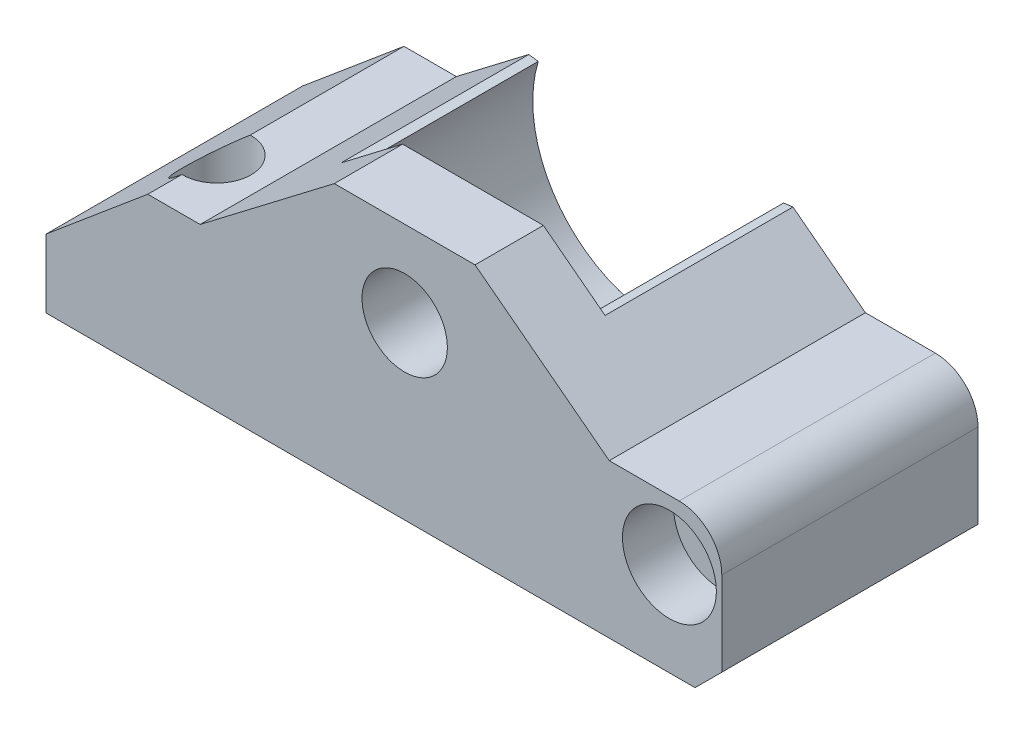
SolidWorks part; units mm, degrees
material "6061-O (SS)"
ref_plane "Piano frontale" through (0, 0, 0) normal (0, 0, 1) x (1, 0, 0)
ref_plane "Piano superiore" through (0, 0, 0) normal (0, 1, 0) x (1, 0, 0)
ref_plane "Piano destro" through (0, 0, 0) normal (1, 0, 0) x (0, 0, -1)
sketch "Schizzo2" plane through (0, 0, 0) normal (0, 0, 1) x (1, 0, 0)
  line L0 (0, 0) -> (38, 0)
  line L1 (0, 0) -> (0, 9)
  line L2 (21, 0) -> (21, 25.5566) construction
  line L3 (0, 9) -> (9.0246, 9)
  line L4 (9.0246, 9) -> (16.8801, 15)
  line L5 (16.8801, 15) -> (25.1199, 15)
  line L6 (32.9754, 9) -> (25.1199, 15)
  line L7 (39.5666, 9) -> (32.9754, 9)
  line L8 (39.5666, 1.5666) -> (38, 0)
  line L11 (39.5666, 9) -> (39.5666, 1.5666)
  circle A0 centre (21, 10) radius 2.5
  circle A1 centre (36.5, 5.5) radius 1.3432
  point P0 (0, 0)
  point P1 (42, 0)
  point P10 (21, 15)
  dimension "D3" = 5
  dimension "D4" = 15
  dimension "D1" = 42
  dimension "D2" = 9
  dimension "D5" = 10
  dimension "D6" = 15.5
  dimension "D7" = 5.5
  dimension "D9" = 4
extrude "Estrusione-Estrusione1" add sketch "Schizzo2" against normal blind 15
sketch "Schizzo3" plane through (0, 0, -15) normal (0, 0, -1) x (-1, 0, 0)
  circle A0 centre (-21, 10) radius 7.5
  dimension "D1" = 15
extrude "Taglio-Estrusione1" cut sketch "Schizzo3" against normal blind 11
sketch "Schizzo4" plane through (0, 0, 0) normal (0, 0, 1) x (1, 0, 0)
  circle A0 centre (36.5, 5.5) radius 2.75
  dimension "D1" = 5.5
extrude "Taglio-Estrusione2" cut sketch "Schizzo4" against normal blind 3
chamfer "Smusso3" distance 1 angle 45 2 edges at (27.9386, 12.8471, -9.5) (14.0614, 12.8471, -9.5) first distance on face at (28.678, 12.2824, -6.3333) first distance on face at (13.322, 12.2824, -6.3333)
fillet "Raccordo1" radius 2.5 1 edges at (39.5666, 9, -7.5)
chamfer "Smusso4" distance 5 angle 50 1 edges at (0, 9, -7.5) first distance on face at (0, 4.5, -7.5)
sketch "Schizzo5" plane through (0, 0, 0) normal (0, -1, 0) x (1, 0, 0)
  line L0 (0, -4) -> (39.5666, -4) construction
  line L1 (0, -15) -> (0, 0) construction
  line L3 (0, 0) -> (38, 0) construction
  circle A0 centre (6, -4) radius 2
  dimension "D3" = 4
  dimension "D1" = 6
  dimension "D2" = 4
extrude "Taglio-Estrusione3" cut sketch "Schizzo5" against normal through all
